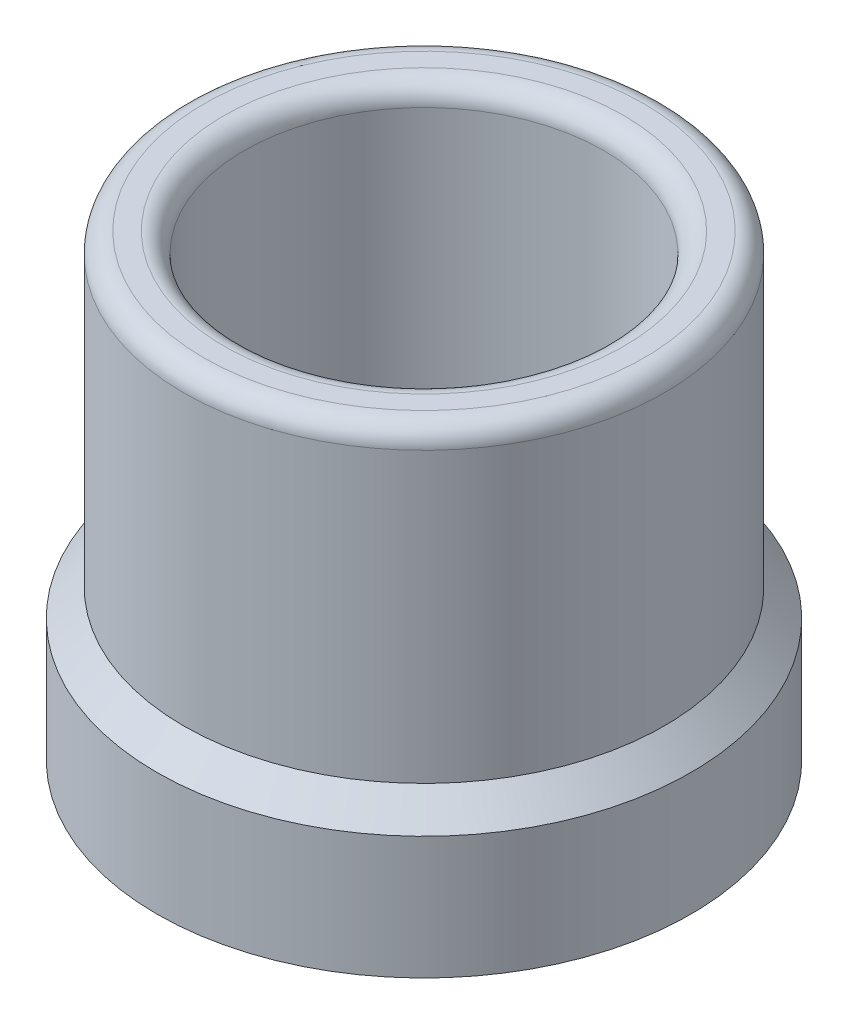
SolidWorks part; units mm, degrees
material "Rubber"
ref_plane "Front Plane" through (0, 0, 0) normal (0, 0, 1) x (1, 0, 0)
ref_plane "Top Plane" through (0, 0, 0) normal (0, 1, 0) x (1, 0, 0)
ref_plane "Right Plane" through (0, 0, 0) normal (1, 0, 0) x (0, 0, -1)
ref_axis "Axis1" through (-26, 76.8998, -3.5) along (0, 1, 0)
ref_plane "PlaneAnt" through (0, 0, -3.5) normal (0, 0, 1) x (1, 0, 0)
sketch "Sketch2" plane through (0, 0, -3.5) normal (0, 0, 1) x (1, 0, 0)
  line L0 (-26, 90.5) -> (-26, 103.8368) construction
  line L1 (-26, 76.8998) -> (-26, 103.8368) construction
  line L2 (-31.5182, 103.8368) -> (-20.4818, 103.8368) construction
  line L3 (-22.8504, 90.5) -> (-29.1496, 90.5) construction
  line L4 (-20.8913, 94.7) -> (-20.8913, 92.5)
  line L5 (-20.1413, 92.25) -> (-20.1413, 92.5) construction
  line L6 (-21.555, 103.8368) -> (-21.555, 96.7375)
  line L7 (-21.555, 96.7375) -> (-22.6756, 96.7375)
  line L8 (-22.6756, 96.7375) -> (-22.6756, 94.7)
  line L9 (-22.6756, 94.7) -> (-21.8913, 94.7)
  line L10 (-30.445, 96.7375) -> (-21.555, 96.7375) construction
  line L12 (-22.6756, 94.7) -> (-20.8913, 94.7) construction
  line L13 (-22.8714, 96.2117) -> (-22.8714, 96.327) construction
  line L14 (-21.555, 96.7375) -> (-21.555, 103.8368) construction
  line L15 (-22, 94.7) -> (-22.6756, 94.7) construction
  line L16 (-20.055, 103.8368) -> (-20.055, 96.2)
  line L17 (-20.055, 96.2) -> (-20.055, 96.2)
  line L18 (-20.055, 96.2) -> (-20.055, 96.2)
  line L20 (-19.3913, 95.5363) -> (-19.3913, 92.5)
  line L21 (-20.8913, 92.5) -> (-19.3913, 92.5) construction
  line L22 (-21.555, 103.8368) -> (-20.055, 103.8368)
  line L23 (-20.055, 96.2) -> (-19.3913, 95.5363)
  line L24 (-19.3913, 96.2) -> (-19.3913, 92.5) construction
  line L25 (-20.055, 96.2) -> (-19.3913, 96.2) construction
  line L26 (-30.5, 92.5) -> (-21.5, 92.5) construction
  arc A0 (-19.3913, 92.5) -> (-20.8913, 92.5) centre (-20.1413, 93.5) cw
  arc A1 (-20.8913, 94.7) -> (-21.8913, 94.7) centre (-21.3913, 94.7) ccw
  point P15 (-20.1413, 92.5)
  dimension "D5" = 1.25
  dimension "D8" = 0.5
  dimension "D1" = 0.5
  dimension "D2" = 0.1957
  dimension "D3" = 7.0993
  dimension "D6" = 0.25
  dimension "D7" = 1.5
  dimension "D9" = 135
  dimension "D4" = 1.5
revolve "Revolve1" add sketch "Sketch2" angle 360 about L0 region at (-20.7843, 97.7663, -3.5)
fillet "Fillet1" radius 0.5 2 edges at (-26, 103.8368, -7.945) (-26, 103.8368, -9.445)
